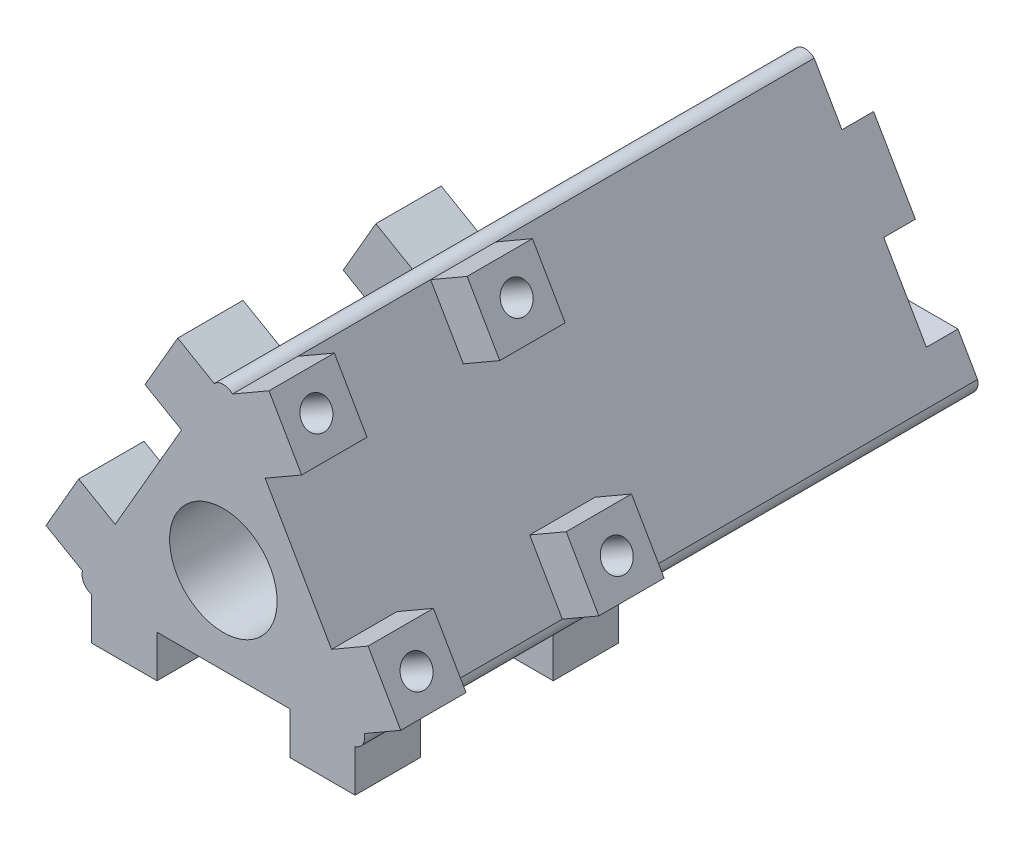
SolidWorks part; units mm, degrees
ref_plane "正面" through (0, 0, 0) normal (0, 0, 1) x (1, 0, 0)
ref_plane "平面" through (0, 0, 0) normal (0, 1, 0) x (1, 0, 0)
ref_plane "右側面" through (0, 0, 0) normal (1, 0, 0) x (0, 0, -1)
sketch "ｽｹｯﾁ1" plane through (0, 0, 0) normal (0, 0, 1) x (1, 0, 0)
  line L0 (0, 21.6506) -> (-12.5, 0)
  line L1 (-12.5, 0) -> (12.5, 0)
  line L2 (12.5, 0) -> (0, 21.6506)
  dimension "D1" = 25
extrude "ﾎﾞｽ - 押し出し1" add sketch "ｽｹｯﾁ1" along normal blind 58.2
sketch "ｽｹｯﾁ2" plane through (-9.375, 5.4127, 0) normal (-0.866, 0.5, 0) x (0, 0, 1)
  line L0 (58.2, -6.25) -> (0, -6.25) construction
  line L1 (58.2, -6.25) -> (52, -6.25)
  line L2 (58.2, -6.25) -> (58.2, -0.05)
  line L3 (58.2, -0.05) -> (52, -0.05)
  line L4 (52, -6.25) -> (52, -0.05)
  line L5 (58.2, 18.75) -> (52, 18.75)
  line L6 (58.2, 18.75) -> (58.2, 12.55)
  line L7 (58.2, 12.55) -> (52, 12.55)
  line L8 (52, 18.75) -> (52, 12.55)
  line L9 (39.4, -6.25) -> (33.2, -6.25)
  line L10 (39.4, -6.25) -> (39.4, -0.05)
  line L11 (39.4, -0.05) -> (33.2, -0.05)
  line L12 (33.2, -6.25) -> (33.2, -0.05)
  line L13 (58.2, 18.75) -> (0, 18.75) construction
  line L14 (39.4, 18.75) -> (33.2, 18.75)
  line L15 (39.4, 18.75) -> (39.4, 12.55)
  line L16 (39.4, 12.55) -> (33.2, 12.55)
  line L17 (33.2, 18.75) -> (33.2, 12.55)
  dimension "D1" = 6.2
  dimension "D2" = 6.2
  dimension "D3" = 6.2
  dimension "D4" = 6.2
  dimension "D5" = 6.2
  dimension "D6" = 6.2
  dimension "D7" = 6.2
  dimension "D8" = 6.2
  dimension "D9" = 25
sketch "ｽｹｯﾁ15" plane through (0, 0, 0) normal (0, -1, 0) x (1, 0, 0)
  line L0 (12.5, 58.2) -> (12.5, 0) construction
  line L1 (-12.5, 58.2) -> (-6.3, 58.2)
  line L2 (-12.5, 58.2) -> (-12.5, 52)
  line L3 (-12.5, 52) -> (-6.3, 52)
  line L4 (-6.3, 58.2) -> (-6.3, 52)
  line L5 (12.5, 58.2) -> (6.3, 58.2)
  line L6 (12.5, 58.2) -> (12.5, 52)
  line L7 (12.5, 52) -> (6.3, 52)
  line L8 (6.3, 58.2) -> (6.3, 52)
  line L9 (12.5, 33.2) -> (6.3, 33.2)
  line L10 (12.5, 33.2) -> (12.5, 39.4)
  line L11 (12.5, 39.4) -> (6.3, 39.4)
  line L12 (6.3, 33.2) -> (6.3, 39.4)
  line L13 (-12.5, 58.2) -> (-12.5, 0) construction
  line L14 (-12.5, 33.2) -> (-6.3, 33.2)
  line L15 (-12.5, 33.2) -> (-12.5, 39.4)
  line L16 (-12.5, 39.4) -> (-6.3, 39.4)
  line L17 (-6.3, 33.2) -> (-6.3, 39.4)
  dimension "D1" = 6.2
  dimension "D2" = 6.2
  dimension "D3" = 6.2
  dimension "D4" = 6.2
  dimension "D5" = 6.2
  dimension "D6" = 6.2
  dimension "D7" = 6.2
  dimension "D8" = 6.2
  dimension "D9" = 25
sketch "ｽｹｯﾁ20" plane through (9.375, 5.4127, 0) normal (0.866, 0.5, 0) x (0, 0, -1)
  line L0 (-58.2, -6.25) -> (0, -6.25) construction
  line L1 (-58.2, -6.25) -> (-52, -6.25)
  line L2 (-58.2, -6.25) -> (-58.2, -0.05)
  line L3 (-58.2, -0.05) -> (-52, -0.05)
  line L4 (-52, -6.25) -> (-52, -0.05)
  line L5 (-58.2, 18.75) -> (-52, 18.75)
  line L6 (-58.2, 18.75) -> (-58.2, 12.55)
  line L7 (-58.2, 12.55) -> (-52, 12.55)
  line L8 (-52, 18.75) -> (-52, 12.55)
  line L9 (-33.2, -6.25) -> (-39.4, -6.25)
  line L10 (-33.2, -6.25) -> (-33.2, -0.05)
  line L11 (-33.2, -0.05) -> (-39.4, -0.05)
  line L12 (-39.4, -6.25) -> (-39.4, -0.05)
  line L13 (-58.2, 18.75) -> (0, 18.75) construction
  line L14 (-33.2, 18.75) -> (-39.4, 18.75)
  line L15 (-33.2, 18.75) -> (-33.2, 12.55)
  line L16 (-33.2, 12.55) -> (-39.4, 12.55)
  line L17 (-39.4, 18.75) -> (-39.4, 12.55)
  dimension "D1" = 6.2
  dimension "D2" = 6.2
  dimension "D3" = 6.2
  dimension "D4" = 6.2
  dimension "D5" = 6.2
  dimension "D6" = 6.2
  dimension "D7" = 6.2
  dimension "D8" = 6.2
  dimension "D9" = 25
sketch "ｽｹｯﾁ11" plane through (0, 0, 0) normal (0, 0, -1) x (-1, 0, 0)
  line L0 (0, 21.6506) -> (12.5, 0)
  line L1 (0, 21.6506) -> (0.866, 22.1506) construction
  line L2 (-0.866, 22.1506) -> (0, 21.6506) construction
  line L3 (0.866, 22.1506) -> (13.366, 0.5)
  line L4 (12.5, 0) -> (-12.5, 0)
  line L5 (-13.366, 0.5) -> (-12.5, 0) construction
  line L6 (-12.5, 0) -> (-12.5, -1) construction
  line L7 (12.5, -1) -> (-12.5, -1)
  line L8 (0, 21.6506) -> (-12.5, 0)
  line L9 (12.5, 0) -> (12.5, -1) construction
  line L10 (12.5, 0) -> (13.366, 0.5) construction
  line L11 (-0.866, 22.1506) -> (-13.366, 0.5)
  arc A0 (-0.866, 22.1506) -> (0.866, 22.1506) centre (0, 21.2846) cw
  arc A1 (13.366, 0.5) -> (12.5, -1) centre (12.183, 0.183) cw
  arc A2 (-12.5, -1) -> (-13.366, 0.5) centre (-12.183, 0.183) cw
  dimension "D1" = 25
  dimension "D2" = 1
  dimension "D3" = 25
  dimension "D4" = 1
  dimension "D5" = 25
  dimension "D6" = 1
extrude "ﾎﾞｽ - 押し出し8" add sketch "ｽｹｯﾁ11" against normal through all
sketch "ｽｹｯﾁ25" plane through (0, 0, 0) normal (0, 0, -1) x (-1, 0, 0)
  line L1 (13.366, 0.5) -> (0.866, 22.1506) construction
  line L2 (0, 7.2169) -> (7.116, 11.3253) construction
  line L3 (0, 7.2169) -> (-7.116, 11.3253) construction
  line L4 (-0.866, 22.1506) -> (-13.366, 0.5) construction
  line L5 (0, 7.2169) -> (0, -1) construction
  line L6 (-12.5, -1) -> (12.5, -1) construction
  circle A0 centre (0, 7.2169) radius 4
  dimension "D1" = 8
extrude "ｶｯﾄ - 押し出し32" cut sketch "ｽｹｯﾁ25" against normal blind 3.5
sketch "ｽｹｯﾁ45" plane through (0, 0, 0) normal (0, 0, -1) x (-1, 0, 0)
  circle A0 centre (0, 7.2169) radius 5.325
  dimension "D1" = 10.65
extrude "ｶｯﾄ - 押し出し33" cut sketch "ｽｹｯﾁ45" against normal blind 3
sketch "ｽｹｯﾁ47" plane through (0, 0, 0) normal (0, 0, -1) x (-1, 0, 0)
  line L0 (3.5, 24.3557) -> (3.5, 10.7169)
  line L1 (13.0117, 10.7169) -> (3.5, 10.7169)
  line L2 (13.0117, 3.7169) -> (13.0117, 10.7169)
  line L3 (13.0117, 3.7169) -> (3.5, 3.7169)
  line L4 (-13.7285, 3.7169) -> (-13.7285, 10.7169)
  line L5 (3.5, 24.3557) -> (-3.5, 24.3557)
  line L6 (-3.5, 24.3557) -> (-3.5, 10.7169)
  line L7 (3.5, -7.4062) -> (-3.5, -7.4062)
  line L8 (-3.5, -7.4062) -> (-3.5, 3.7169)
  line L9 (3.5, -7.4062) -> (3.5, 3.7169)
  line L10 (-3.5, 3.7169) -> (-13.7285, 3.7169)
  line L11 (-3.5, 10.7169) -> (-13.7285, 10.7169)
  line L12 (0, 7.2169) -> (3.5, 3.7169) construction
  line L13 (0, 7.2169) -> (-3.5, 3.7169) construction
  line L14 (-3.5, 3.7169) -> (-3.51, 3.7416) construction
  line L15 (0, 7.2169) -> (3.5, 10.7169) construction
  line L16 (3.5, 10.7169) -> (3.5321, 10.6819) construction
  line L17 (0, 7.2169) -> (-3.5, 10.7169) construction
  dimension "D1" = 7
  dimension "D2" = 7
extrude "ｶｯﾄ - 押し出し34" cut sketch "ｽｹｯﾁ47" against normal blind 3
sketch "ｽｹｯﾁ48" plane through (0, 0, 58.2) normal (0, 0, 1) x (1, 0, 0)
  line L0 (0, 7.2169) -> (0, -1) construction
  line L1 (12.5, -1) -> (-12.5, -1) construction
  line L2 (0, 7.2169) -> (7.116, 11.3253) construction
  line L3 (0.866, 22.1506) -> (13.366, 0.5) construction
  line L4 (0, 7.2169) -> (-7.116, 11.3253) construction
  line L5 (-13.366, 0.5) -> (-0.866, 22.1506) construction
  circle A0 centre (0, 7.2169) radius 5.1
  dimension "D1" = 10.2
extrude "ｶｯﾄ - 押し出し35" cut sketch "ｽｹｯﾁ48" against normal blind 10
extrude "ﾎﾞｽ - 押し出し14" add sketch "ｽｹｯﾁ15" along normal blind 5
extrude "ﾎﾞｽ - 押し出し15" add sketch "ｽｹｯﾁ2" along normal blind 5
extrude "ﾎﾞｽ - 押し出し16" add sketch "ｽｹｯﾁ20" along normal blind 5
sketch "ｽｹｯﾁ50" plane through (13.7051, 7.9127, 0) normal (0.866, 0.5, 0) x (0, 0, -1)
  line L1 (-39.4, -6.25) -> (-33.2, -6.25) construction
  line L2 (-33.2, -6.25) -> (-33.2, -0.05) construction
  line L3 (-58.2, -0.05) -> (-58.2, -6.25) construction
  line L4 (-58.2, -6.25) -> (-52, -6.25) construction
  line L5 (-58.2, 18.75) -> (-52, 18.75) construction
  line L6 (-58.2, 18.75) -> (-58.2, 12.55) construction
  line L7 (-33.2, 12.55) -> (-33.2, 18.75) construction
  line L8 (-33.2, 18.75) -> (-39.4, 18.75) construction
  circle A0 centre (-55.2, -3.25) radius 1.4
  circle A1 centre (-55.2, 15.75) radius 1.4
  circle A2 centre (-36.2, 15.75) radius 1.4
  circle A3 centre (-36.2, -3.25) radius 1.4
  dimension "D1" = 2.8
  dimension "D2" = 2.8
  dimension "D3" = 2.8
  dimension "D4" = 2.8
  dimension "D5" = 3
  dimension "D7" = 3
  dimension "D8" = 3
  dimension "D9" = 3
  dimension "D10" = 3
  dimension "D11" = 3
  dimension "D12" = 3
  dimension "D6" = 3
extrude "ｶｯﾄ - 押し出し36" cut sketch "ｽｹｯﾁ50" against normal blind 5
sketch "ｽｹｯﾁ51" plane through (0, -5, 0) normal (0, -1, 0) x (1, 0, 0)
  line L0 (6.3, 33.2) -> (12.5, 33.2) construction
  line L1 (12.5, 33.2) -> (12.5, 39.4) construction
  line L2 (12.5, 52) -> (12.5, 58.2) construction
  line L3 (12.5, 58.2) -> (6.3, 58.2) construction
  line L4 (-6.3, 58.2) -> (-12.5, 58.2) construction
  line L5 (-12.5, 58.2) -> (-12.5, 52) construction
  line L6 (-12.5, 39.4) -> (-12.5, 33.2) construction
  line L7 (-12.5, 33.2) -> (-6.3, 33.2) construction
  circle A0 centre (-9.5, 55.2) radius 1.4
  circle A1 centre (9.5, 55.2) radius 1.4
  circle A2 centre (9.5, 36.2) radius 1.4
  circle A3 centre (-9.5, 36.2) radius 1.4
  dimension "D1" = 2.8
  dimension "D2" = 2.8
  dimension "D3" = 2.8
  dimension "D4" = 2.8
  dimension "D7" = 3
  dimension "D8" = 3
  dimension "D9" = 3
  dimension "D10" = 3
  dimension "D12" = 3
  dimension "D5" = 3
  dimension "D6" = 3
  dimension "D11" = 3
extrude "ｶｯﾄ - 押し出し37" cut sketch "ｽｹｯﾁ51" against normal blind 5
sketch "ｽｹｯﾁ52" plane through (-13.7051, 7.9127, 0) normal (-0.866, 0.5, 0) x (0, 0, 1)
  line L0 (58.2, 12.55) -> (58.2, 18.75) construction
  line L1 (58.2, 18.75) -> (52, 18.75) construction
  line L2 (33.2, 18.75) -> (33.2, 12.55) construction
  line L3 (39.4, 18.75) -> (33.2, 18.75) construction
  line L4 (52, -6.25) -> (58.2, -6.25) construction
  line L5 (58.2, -6.25) -> (58.2, -0.05) construction
  circle A0 centre (55.2, -3.25) radius 1.4
  circle A1 centre (36.9618, -3.3056) radius 1.4
  circle A2 centre (36.2, 15.75) radius 1.4
  circle A3 centre (55.2, 15.75) radius 1.4
  dimension "D1" = 2.8
  dimension "D2" = 2.8
  dimension "D3" = 2.8
  dimension "D4" = 2.8
  dimension "D5" = 3
  dimension "D7" = 3
  dimension "D10" = 3
  dimension "D6" = 3
  dimension "D8" = 3
  dimension "D9" = 3
extrude "ｶｯﾄ - 押し出し38" cut sketch "ｽｹｯﾁ52" against normal blind 5
